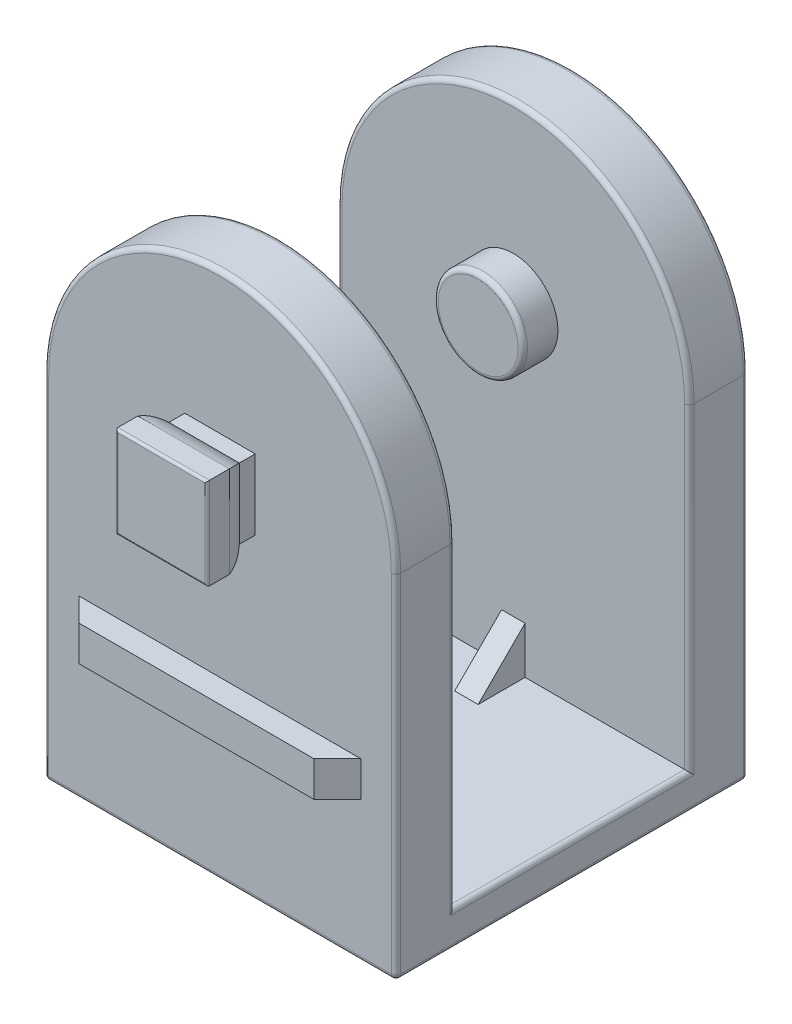
SolidWorks part; units mm, degrees
ref_plane "前视基准面" through (0, 0, 0) normal (0, 0, 1) x (1, 0, 0)
ref_plane "上视基准面" through (0, 0, 0) normal (0, 1, 0) x (1, 0, 0)
ref_plane "右视基准面" through (0, 0, 0) normal (1, 0, 0) x (0, 0, -1)
sketch "草图1" plane through (0, 0, 0) normal (0, 0, 1) x (1, 0, 0)
  line L1 (-7.5, 0) -> (7.5, 0)
  line L2 (-7.5, 0) -> (-7.5, 15)
  line L4 (7.5, 0) -> (7.5, 15)
  arc A0 (7.5, 15) -> (-7.5, 15) centre (0, 15) ccw
extrude "凸台-拉伸1" add sketch "草图1" along normal blind 7.5 and the other way blind 7.5
sketch "草图3" plane through (-7.5, 0, 0) normal (-1, 0, 0) x (0, 0, 1)
  line L1 (7.5, 22.5) -> (-7.5, 22.5) construction
  line L2 (-5, 1.5) -> (5, 1.5)
  line L3 (-5, 1.5) -> (-5, 22.5)
  line L4 (-5, 22.5) -> (5, 22.5)
  line L6 (5, 1.5) -> (5, 22.5)
extrude "切除-拉伸1" cut sketch "草图3" against normal through all
sketch "草图4" plane through (0, 0, 0) normal (0, -1, 0) x (-1, 0, 0)
  line L1 (1.5, 1.5) -> (-1.5, 1.5)
  line L2 (1.5, 1.5) -> (1.5, -1.5)
  line L3 (1.5, -1.5) -> (-1.5, -1.5)
  line L4 (-1.5, 1.5) -> (-1.5, -1.5)
extrude "凸台-拉伸2" add sketch "草图4" along normal blind 1
sketch "草图5" plane through (0, 0, 0) normal (0, 0, 1) x (1, 0, 0)
  line L0 (-1.95, -2.5) -> (1.95, -2.5)
  line L1 (-1.95, -2.5) -> (-1.95, -1.5556)
  line L2 (1.95, -2.5) -> (1.95, -1.5556)
  line L4 (-1.5, -1) -> (-1.5, 0) construction
  line L5 (-1.5, -0.6771) -> (1.5, -0.6771)
  arc A0 (-1.5, -0.6771) -> (-1.95, -1.5556) centre (0, -2) ccw
  arc A1 (1.95, -1.5556) -> (1.5, -0.6771) centre (0, -2) ccw
extrude "凸台-拉伸3" add sketch "草图5" along normal blind 2 and the other way blind 2
sketch "草图6" plane through (-1.95, 0, 0) normal (-1, 0, 0) x (0, 0, 1)
  line L0 (-1.95, -2.5) -> (-1.95, -1.5556)
  line L1 (-2, -2.5) -> (-1.95, -2.5)
  line L2 (-2, -2.5) -> (-2, -0.6771)
  line L3 (-2, -0.6771) -> (-1.5, -0.6771)
  line L4 (2, -2.5) -> (2, -0.6771)
  line L6 (1.5, -0.6771) -> (2, -0.6771)
  line L7 (1.95, -1.5556) -> (1.95, -2.5)
  line L8 (1.95, -2.5) -> (2, -2.5)
  arc A1 (-1.5, -0.6771) -> (-1.95, -1.5556) centre (0, -2) ccw
  arc A2 (1.95, -1.5556) -> (1.5, -0.6771) centre (0, -2) ccw
extrude "切除-拉伸2" cut sketch "草图6" against normal up to next
sketch "草图7" plane through (0, 0, 7.5) normal (0, 0, 1) x (1, 0, 0)
  line L1 (-1.5, 13.5) -> (1.5, 13.5)
  line L2 (-1.5, 13.5) -> (-1.5, 16.5)
  line L3 (-1.5, 16.5) -> (1.5, 16.5)
  line L4 (1.5, 13.5) -> (1.5, 16.5)
extrude "凸台-拉伸4" add sketch "草图7" along normal blind 1
sketch "草图8" plane through (0, 16.5, 0) normal (0, 1, 0) x (1, 0, 0)
  line L0 (-1.95, -10) -> (1.95, -10)
  line L1 (-1.95, -10) -> (-1.95, -9.0556)
  line L2 (1.95, -9.0556) -> (1.95, -10)
  line L5 (-1.5, -8.5) -> (-1.5, -7.5) construction
  line L6 (-1.5, -8.1771) -> (1.5, -8.1771)
  arc A0 (1.95, -9.0556) -> (1.5, -8.1771) centre (0, -9.5) ccw
  arc A1 (-1.5, -8.1771) -> (-1.95, -9.0556) centre (0, -9.5) ccw
extrude "凸台-拉伸5" add sketch "草图8" along normal blind 1 and the other way blind 4
sketch "草图9" plane through (-1.95, 0, 0) normal (-1, 0, 0) x (0, 0, 1)
  line L0 (10, 16.95) -> (9.0556, 16.95)
  line L1 (10, 17.5) -> (8.1771, 17.5)
  line L2 (10, 17.5) -> (10, 16.95)
  line L3 (10, 12.5) -> (8.1771, 12.5)
  line L4 (8.1771, 17.5) -> (8.1771, 16.5)
  line L5 (9.0556, 13.05) -> (10, 13.05)
  line L6 (10, 13.05) -> (10, 12.5)
  line L7 (8.1771, 13.5) -> (8.1771, 12.5)
  arc A0 (8.1771, 13.5) -> (9.0556, 13.05) centre (9.5, 15) ccw
  arc A1 (9.0556, 16.95) -> (8.1771, 16.5) centre (9.5, 15) ccw
extrude "切除-拉伸3" cut sketch "草图9" against normal up to next
sketch "草图10" plane through (0, 0, -5) normal (0, 0, 1) x (1, 0, 0)
  circle A0 centre (0, 15) radius 1.9
extrude "凸台-拉伸6" add sketch "草图10" along normal blind 1.5
sketch "草图11" plane through (0, 0, 5) normal (0, 0, -1) x (-1, 0, 0)
  circle A0 centre (0, 15) radius 1.9
extrude "凸台-拉伸7" add sketch "草图11" along normal blind 1.5
mirror "镜向1" about plane through (0, 0, 0) normal (0, 0, 1) of "凸台-拉伸4", "凸台-拉伸5", "切除-拉伸3"
sketch "草图12" plane through (0, 0, 0) normal (1, 0, 0) x (0, 0, -1)
  line L0 (5, 1.5) -> (3, 1.5)
  line L1 (5, 1.5) -> (-5, 1.5) construction
  line L2 (3, 1.5) -> (5, 3.5)
  line L3 (5, 15) -> (5, 1.5) construction
  line L4 (5, 3.5) -> (5, 1.5)
  line L5 (-5, 1.5) -> (-3, 1.5)
  line L6 (-3, 1.5) -> (-5, 3.5)
  line L7 (-5, 1.5) -> (-5, 15) construction
  line L8 (-5, 3.5) -> (-5, 1.5)
extrude "凸台-拉伸8" add sketch "草图12" along normal blind 0.5 and the other way blind 0.5
sketch "草图13" plane through (0, 0, 7.5) normal (0, 0, 1) x (1, 0, 0)
  line L1 (-6, 6) -> (6, 6)
  line L2 (-6, 6) -> (-6, 7.5)
  line L3 (-6, 7.5) -> (6, 7.5)
  line L4 (6, 6) -> (6, 7.5)
  dimension "D1" = 1.5
  dimension "D2" = 12
  dimension "D3" = 6
extrude "凸台-拉伸9" add sketch "草图13" along normal blind 1
chamfer "倒角1" distance 1 angle 45 2 edges at (-6, 6.75, 8.5) (6, 6.75, 8.5)
mirror "镜向2" about plane through (0, 0, 0) normal (0, 0, 1) of "凸台-拉伸9", "倒角1"
fillet "圆角1" radius 0.1 8 edges at (1.95, 15, -10) (0, 16.95, -10) (-1.95, 15, -10) (0, 13.05, -10) (-1.95, 15, 10) (0, 16.95, 10) (1.95, 15, 10) (0, 13.05, 10)
fillet "圆角2" radius 0.2 18 edges at (-7.5, 1.5, 0) (-7.5, 8.25, 5) (-7.5, 7.5, 7.5) (-7.5, 0, 0) (-7.5, 7.5, -7.5) (-7.5, 8.25, -5) (0, 22.5, -7.5) (0, 22.5, -5) (0, 22.5, 7.5) (0, 22.5, 5) (7.5, 7.5, -7.5) (7.5, 0, 0) (7.5, 7.5, 7.5) (7.5, 8.25, 5) (7.5, 1.5, 0) (7.5, 8.25, -5) (0, 0, -7.5) (0, 0, 7.5)
fillet "圆角3" radius 0.2 2 edges at (-1.9, 15, 3.5) (1.9, 15, -3.5)
fillet "圆角4" radius 0.1 4 edges at (1.95, -2.5, 0) (0, -2.5, -1.95) (-1.95, -2.5, 0) (0, -2.5, 1.95)
